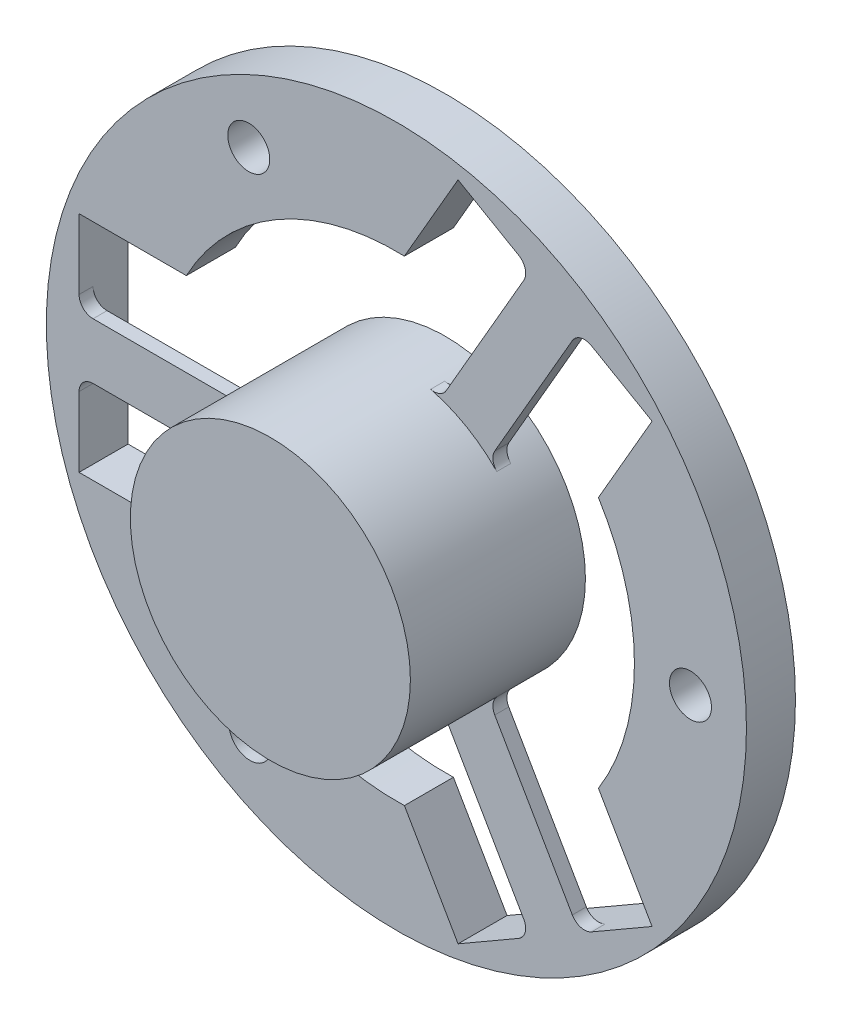
SolidWorks part; units mm, degrees
note: The reader was unsure of these and kept them because the rebuilt part matched: shared geometry of "Sketch1<3>".
ref_plane "Front Plane" through (0, 0, 0) normal (0, 0, 1) x (1, 0, 0)
ref_plane "Top Plane" through (0, 0, 0) normal (0, 1, 0) x (1, 0, 0)
ref_plane "Right Plane" through (0, 0, 0) normal (1, 0, 0) x (0, 0, -1)
sketch "Sketch1" plane through (0, 0, 0) normal (0, 0, 1) x (1, 0, 0)
  circle A0 centre (0, 0) radius 25
  circle A1 centre (0, 0) radius 10
  dimension "D1" = 50
  dimension "D2" = 20
extrude "Boss-Extrude1" add sketch "Sketch1" along normal blind 9 and the other way blind 3.5 contours A1
extrude "Boss-Extrude2" add sketch "Sketch1<3>" against normal blind 3.5 separate body
sketch "Sketch1<3>" plane through (0, 0, 0) normal (0, 0, 1) x (1, 0, 0) same geometry as "Sketch1"
sketch "Sketch3" plane through (0, 0, 0) normal (0, 0, 1) x (1, 0, 0)
  circle A0 centre (0, 0) radius 17
  dimension "D1" = 34
extrude "Cut-Extrude1" cut sketch "Sketch3" against normal blind 3.5
sketch "Sketch8" plane through (0, 0, 0) normal (0, 0, 1) x (1, 0, 0)
  line L1 (-22.6618, 8) -> (-13.6618, 8)
  line L2 (-22.6618, 8) -> (-22.6618, -8)
  line L3 (-22.6618, -8) -> (-13.6618, -8)
  line L4 (-13.6618, 8) -> (-13.6618, -8)
  line L5 (-22.6618, 8) -> (-13.6618, -8) construction
  line L6 (-22.6618, -8) -> (-13.6618, 8) construction
  point P0 (-18.1618, 0)
  dimension "D1" = 9
  dimension "D2" = 16
extrude "Cut-Extrude3" cut sketch "Sketch8" against normal through all
sketch "Sketch10" plane through (0, 0, 0) normal (0, 0, 1) x (1, 0, 0)
  line L0 (-10, 0) -> (-25, 0) construction
  line L1 (-22.6618, 8) -> (-22.6618, -8) construction
  line L2 (-22.6618, 2) -> (-9.798, 2)
  line L3 (-22.6618, 2) -> (-22.6618, -2)
  line L4 (-22.6618, -2) -> (-9.798, -2)
  line L5 (-9.798, 2) -> (-9.798, -2)
  circle A0 centre (0, 0) radius 10 construction
  circle A1 centre (0, 0) radius 25 construction
  dimension "D1" = 4
  dimension "D2" = 2
extrude "Boss-Extrude4" add sketch "Sketch10" against normal blind 1
pattern_circular "CirPattern2" count 3 over 360 about axis through (0, 0, 0) along (0, 0, 1) of "Cut-Extrude3", "Boss-Extrude4"
hole_wizard "Ø3.0mm Dowel Hole1" positions "Sketch13" profile "Sketch14" hole size "Ø3.0" standard "ANSI Metric" end condition through all
sketch "Sketch13" plane through (0, 0, 0) normal (0, 0, 1) x (1, 0, 0)
  line L0 (0, 0) -> (-15.2081, 26.1945) construction
  point P0 (-10.544, 18.161)
  dimension "D1" = 21
sketch "Sketch14" plane through (-10.544, 18.161, 0) normal (1, 0, 0) x (0, -1, 0)
  line L0 (0, 0) -> (0, 3.5)
  line L1 (0, 3.5) -> (1.5, 3.5)
  line L2 (1.5, 3.5) -> (1.5, 0)
  line L5 (1.5, 0) -> (0, 0)
  line L11 (0, -6.35) -> (0, 107.95) construction
  dimension "Thru Hole Dia." = 3
  dimension "Thru Hole Depth" = 3.5
pattern_circular "CirPattern3" count 3 over 360 about axis through (0, 0, 0) along (0, 0, 1) of "Ø3.0mm Dowel Hole1"
fillet "Fillet1" radius 1 1 edges at (9.5988, 20.6257, -0.5)
fillet "Fillet2" radius 1 1 edges at (13.0629, 18.6257, -0.5)
fillet "Fillet3" radius 1 1 edges at (6.631, 7.4853, -0.5)
fillet "Fillet4" radius 1 1 edges at (3.1669, 9.4853, -0.5)
fillet "Fillet5" radius 1 1 edges at (-22.6618, 2, -0.5)
fillet "Fillet6" radius 1 1 edges at (-9.798, 2, -0.5)
fillet "Fillet7" radius 1 1 edges at (-22.6618, -2, -0.5)
fillet "Fillet8" radius 1 1 edges at (-9.798, -2, -0.5)
fillet "Fillet9" radius 1 1 edges at (3.1669, -9.4853, -0.5)
fillet "Fillet10" radius 1 1 edges at (6.631, -7.4853, -0.5)
fillet "Fillet11" radius 1 1 edges at (9.5988, -20.6257, -0.5)
fillet "Fillet12" radius 1 1 edges at (13.0629, -18.6257, -0.5)
